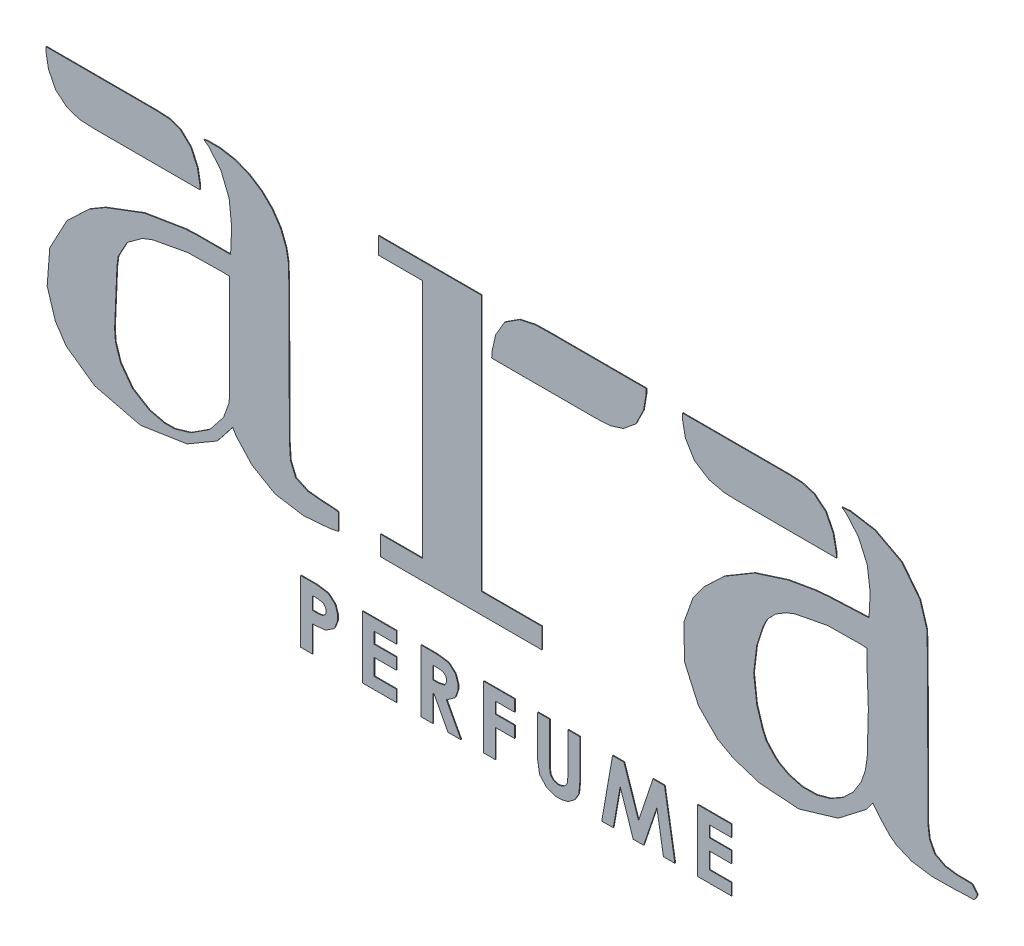
SolidWorks part; units mm, degrees
ref_plane "Front Plane" through (0, 0, 0) normal (0, 0, 1) x (1, 0, 0)
ref_plane "Top Plane" through (0, 0, 0) normal (0, 1, 0) x (1, 0, 0)
ref_plane "Right Plane" through (0, 0, 0) normal (1, 0, 0) x (0, 0, -1)
sketch "Model" plane through (0, 0, 0) normal (0, 0, 1) x (1, 0, 0)
  line L0 (1544.5765, 1861.6625) -> (1535.651, 1862.3255)
  line L1 (1535.651, 1862.3255) -> (1490.4999, 1861.7616)
  line L2 (1490.4999, 1861.7616) -> (1445.6232, 1853.1586)
  line L3 (1445.6232, 1853.1586) -> (1436.8704, 1849.7626)
  line L4 (1436.8704, 1849.7626) -> (1433.8681, 1848.6425)
  line L5 (1433.8681, 1848.6425) -> (1418.9837, 1839.6458)
  line L6 (1418.9837, 1839.6458) -> (1407.3708, 1827.4614)
  line L7 (1407.3708, 1827.4614) -> (1406.0373, 1824.736)
  line L8 (1406.0373, 1824.736) -> (1401.9784, 1816.4378)
  line L9 (1401.9784, 1816.4378) -> (1393.2941, 1789.7983)
  line L10 (1393.2941, 1789.7983) -> (1389.0295, 1754.5583)
  line L11 (1389.0295, 1754.5583) -> (1393.1875, 1719.1634)
  line L12 (1393.1875, 1719.1634) -> (1401.6634, 1692.3182)
  line L13 (1401.6634, 1692.3182) -> (1405.6512, 1683.8854)
  line L14 (1405.6512, 1683.8854) -> (1406.3497, 1682.3436)
  line L15 (1406.3497, 1682.3436) -> (1418.43, 1669.0823)
  line L16 (1418.43, 1669.0823) -> (1419.7914, 1667.9621)
  line L17 (1419.7914, 1667.9621) -> (1423.6802, 1664.7719)
  line L18 (1423.6802, 1664.7719) -> (1437.2539, 1657.4262)
  line L19 (1437.2539, 1657.4262) -> (1456.1972, 1652.4173)
  line L20 (1456.1972, 1652.4173) -> (1475.5876, 1652.6942)
  line L21 (1475.5876, 1652.6942) -> (1494.3531, 1657.8809)
  line L22 (1494.3531, 1657.8809) -> (1511.5032, 1667.6395)
  line L23 (1511.5032, 1667.6395) -> (1526.0625, 1681.6451)
  line L24 (1526.0625, 1681.6451) -> (1536.9413, 1699.5318)
  line L25 (1536.9413, 1699.5318) -> (1542.3718, 1715.4906)
  line L26 (1542.3718, 1715.4906) -> (1543.2126, 1720.9541)
  line L27 (1543.2126, 1720.9541) -> (1544.9601, 1732.3613)
  line L28 (1544.9601, 1732.3613) -> (1546.5019, 1790.4993)
  line L29 (1546.5019, 1790.4993) -> (1544.5765, 1843.8774)
  line L30 (1544.5765, 1843.8774) -> (1544.5765, 1861.6625)
  line L31 (1552.4175, 1681.7899) -> (1543.3116, 1669.3617)
  line L32 (1543.3116, 1669.3617) -> (1505.1938, 1639.9256)
  line L33 (1505.1938, 1639.9256) -> (1451.0817, 1623.822)
  line L34 (1451.0817, 1623.822) -> (1397.0406, 1627.6041)
  line L35 (1397.0406, 1627.6041) -> (1360.8837, 1639.3236)
  line L36 (1360.8837, 1639.3236) -> (1350.0329, 1645.3104)
  line L37 (1350.0329, 1645.3104) -> (1339.5681, 1651.0889)
  line L38 (1339.5681, 1651.0889) -> (1313.3121, 1677.5506)
  line L39 (1313.3121, 1677.5506) -> (1293.9217, 1720.4995)
  line L40 (1293.9217, 1720.4995) -> (1293.2943, 1767.5758)
  line L41 (1293.2943, 1767.5758) -> (1305.8572, 1802.6482)
  line L42 (1305.8572, 1802.6482) -> (1312.9006, 1812.2367)
  line L43 (1312.9006, 1812.2367) -> (1320.3834, 1822.5313)
  line L44 (1320.3834, 1822.5313) -> (1348.4911, 1849.3054)
  line L45 (1348.4911, 1849.3054) -> (1390.1141, 1873.9841)
  line L46 (1390.1141, 1873.9841) -> (1436.4589, 1888.8227)
  line L47 (1436.4589, 1888.8227) -> (1473.8045, 1895.2286)
  line L48 (1473.8045, 1895.2286) -> (1486.3318, 1896.3488)
  line L49 (1486.3318, 1896.3488) -> (1491.3051, 1896.806)
  line L50 (1491.3051, 1896.806) -> (1541.9502, 1899.1097)
  line L51 (1541.9502, 1899.1097) -> (1547.1292, 1899.3612)
  line L52 (1547.1292, 1899.3612) -> (1548.0081, 1907.2987)
  line L53 (1548.0081, 1907.2987) -> (1548.8768, 1931.3144)
  line L54 (1548.8768, 1931.3144) -> (1545.0337, 1961.1696)
  line L55 (1545.0337, 1961.1696) -> (1532.9535, 1988.3653)
  line L56 (1532.9535, 1988.3653) -> (1516.573, 2007.4433)
  line L57 (1516.573, 2007.4433) -> (1510.0605, 2012.3785)
  line L58 (1510.0605, 2012.3785) -> (1521.2974, 2013.1862)
  line L59 (1521.2974, 2013.1862) -> (1555.6332, 2007.55)
  line L60 (1555.6332, 2007.55) -> (1592.4606, 1987.8802)
  line L61 (1592.4606, 1987.8802) -> (1617.345, 1955.9905)
  line L62 (1617.345, 1955.9905) -> (1626.87, 1924.906)
  line L63 (1626.87, 1924.906) -> (1627.1469, 1914.4767)
  line L64 (1627.1469, 1914.4767) -> (1627.6041, 1896.5901)
  line L65 (1627.6041, 1896.5901) -> (1628.3737, 1717.487)
  line L66 (1628.3737, 1717.487) -> (1628.4016, 1699.5673)
  line L67 (1628.4016, 1699.5673) -> (1628.4016, 1694.0733)
  line L68 (1628.4016, 1694.0733) -> (1630.5073, 1677.5506)
  line L69 (1630.5073, 1677.5506) -> (1637.7209, 1663.5095)
  line L70 (1637.7209, 1663.5095) -> (1651.4394, 1656.0546)
  line L71 (1651.4394, 1656.0546) -> (1667.7488, 1653.7864)
  line L72 (1667.7488, 1653.7864) -> (1673.2047, 1653.7153)
  line L73 (1673.2047, 1653.7153) -> (1674.5026, 1653.7153)
  line L74 (1674.5026, 1653.7153) -> (1687.5227, 1653.4994)
  line L75 (1687.5227, 1653.4994) -> (1688.7165, 1653.1158)
  line L76 (1688.7165, 1653.1158) -> (1689.4861, 1652.872)
  line L77 (1689.4861, 1652.872) -> (1695.8208, 1645.2393)
  line L78 (1695.8208, 1645.2393) -> (1695.991, 1644.3706)
  line L79 (1695.991, 1644.3706) -> (1696.0977, 1643.7686)
  line L80 (1696.0977, 1643.7686) -> (1694.2791, 1639.2525)
  line L81 (1694.2791, 1639.2525) -> (1691.2692, 1636.0013)
  line L82 (1691.2692, 1636.0013) -> (1690.812, 1636.0013)
  line L83 (1690.812, 1636.0013) -> (1683.6441, 1636.108)
  line L84 (1683.6441, 1636.108) -> (1662.1125, 1635.2291)
  line L85 (1662.1125, 1635.2291) -> (1633.4816, 1634.9523)
  line L86 (1633.4816, 1634.9523) -> (1605.6229, 1639.2525)
  line L87 (1605.6229, 1639.2525) -> (1585.0413, 1647.9723)
  line L88 (1585.0413, 1647.9723) -> (1579.2272, 1652.2446)
  line L89 (1579.2272, 1652.2446) -> (1576.672, 1654.1369)
  line L90 (1576.672, 1654.1369) -> (1565.5442, 1665.8565)
  line L91 (1565.5442, 1665.8565) -> (1554.7645, 1679.1635)
  line L92 (1554.7645, 1679.1635) -> (1552.4175, 1681.7899)
  line L93 (669.2773, 1866.3488) -> (659.6151, 1866.806)
  line L94 (659.6151, 1866.806) -> (611.4542, 1865.9653)
  line L95 (611.4542, 1865.9653) -> (563.9206, 1857.1464)
  line L96 (563.9206, 1857.1464) -> (554.6446, 1853.6082)
  line L97 (554.6446, 1853.6082) -> (549.463, 1851.6549)
  line L98 (549.463, 1851.6549) -> (528.3581, 1836.1787)
  line L99 (528.3581, 1836.1787) -> (516.1763, 1813.7073)
  line L100 (516.1763, 1813.7073) -> (515.5133, 1808.2489)
  line L101 (515.5133, 1808.2489) -> (514.5329, 1800.7584)
  line L102 (514.5329, 1800.7584) -> (511.3122, 1724.8708)
  line L103 (511.3122, 1724.8708) -> (511.9065, 1717.3448)
  line L104 (511.9065, 1717.3448) -> (512.4323, 1710.0677)
  line L105 (512.4323, 1710.0677) -> (519.4681, 1688.5361)
  line L106 (519.4681, 1688.5361) -> (535.9883, 1666.2781)
  line L107 (535.9883, 1666.2781) -> (559.1581, 1652.0312)
  line L108 (559.1581, 1652.0312) -> (579.9506, 1647.1646)
  line L109 (579.9506, 1647.1646) -> (586.8467, 1647.2357)
  line L110 (586.8467, 1647.2357) -> (594.1619, 1647.3449)
  line L111 (594.1619, 1647.3449) -> (616.1075, 1653.8499)
  line L112 (616.1075, 1653.8499) -> (642.1145, 1670.7231)
  line L113 (642.1145, 1670.7231) -> (661.0147, 1694.7718)
  line L114 (661.0147, 1694.7718) -> (668.6118, 1715.7395)
  line L115 (668.6118, 1715.7395) -> (668.8912, 1722.8109)
  line L116 (668.8912, 1722.8109) -> (669.2773, 1734.5304)
  line L117 (669.2773, 1734.5304) -> (669.2773, 1833.4101)
  line L118 (669.2773, 1833.4101) -> (669.2773, 1866.3488)
  line L119 (670.5016, 1893.0239) -> (671.1315, 1901.5634)
  line L120 (671.1315, 1901.5634) -> (671.9367, 1927.2555)
  line L121 (671.9367, 1927.2555) -> (668.6474, 1958.7591)
  line L122 (668.6474, 1958.7591) -> (657.0955, 1987.0395)
  line L123 (657.0955, 1987.0395) -> (640.5042, 2006.5365)
  line L124 (640.5042, 2006.5365) -> (633.8189, 2011.4387)
  line L125 (633.8189, 2011.4387) -> (639.1402, 2012.2083)
  line L126 (639.1402, 2012.2083) -> (655.5562, 2012.2363)
  line L127 (655.5562, 2012.2363) -> (676.4528, 2008.599)
  line L128 (676.4528, 2008.599) -> (695.8432, 2000.9739)
  line L129 (695.8432, 2000.9739) -> (713.1329, 1989.8081)
  line L130 (713.1329, 1989.8081) -> (727.8014, 1975.5968)
  line L131 (727.8014, 1975.5968) -> (739.2111, 1958.7235)
  line L132 (739.2111, 1958.7235) -> (746.8057, 1939.6837)
  line L133 (746.8057, 1939.6837) -> (749.7826, 1924.1364)
  line L134 (749.7826, 1924.1364) -> (749.9553, 1918.9217)
  line L135 (749.9553, 1918.9217) -> (750.5167, 1902.3355)
  line L136 (750.5167, 1902.3355) -> (751.2863, 1736.1789)
  line L137 (751.2863, 1736.1789) -> (751.3574, 1719.5495)
  line L138 (751.3574, 1719.5495) -> (751.3574, 1711.9956)
  line L139 (751.3574, 1711.9956) -> (752.8966, 1689.2092)
  line L140 (752.8966, 1689.2092) -> (760.001, 1672.1912)
  line L141 (760.001, 1672.1912) -> (776.5237, 1664.495)
  line L142 (776.5237, 1664.495) -> (798.8529, 1662.2903)
  line L143 (798.8529, 1662.2903) -> (806.3459, 1662.0388)
  line L144 (806.3459, 1662.0388) -> (807.2907, 1662.0388)
  line L145 (807.2907, 1662.0388) -> (817.4761, 1661.0279)
  line L146 (817.4761, 1661.0279) -> (818.7004, 1660.8831)
  line L147 (818.7004, 1660.8831) -> (818.7004, 1655.1478)
  line L148 (818.7004, 1655.1478) -> (818.7004, 1642.2014)
  line L149 (818.7004, 1642.2014) -> (818.7004, 1637.8555)
  line L150 (818.7004, 1637.8555) -> (806.9758, 1635.4095)
  line L151 (806.9758, 1635.4095) -> (770.8875, 1632.5063)
  line L152 (770.8875, 1632.5063) -> (731.7562, 1638.841)
  line L153 (731.7562, 1638.841) -> (699.7649, 1657.4973)
  line L154 (699.7649, 1657.4973) -> (678.8328, 1680.4183)
  line L155 (678.8328, 1680.4183) -> (673.4073, 1689.0289)
  line L156 (673.4073, 1689.0289) -> (672.3583, 1687.703)
  line L157 (672.3583, 1687.703) -> (662.3456, 1674.8531)
  line L158 (662.3456, 1674.8531) -> (661.3652, 1673.5908)
  line L159 (661.3652, 1673.5908) -> (652.0891, 1662.0033)
  line L160 (652.0891, 1662.0033) -> (610.7532, 1637.8911)
  line L161 (610.7532, 1637.8911) -> (546.768, 1628.0892)
  line L162 (546.768, 1628.0892) -> (483.8344, 1643.5984)
  line L163 (483.8344, 1643.5984) -> (444.7362, 1671.3225)
  line L164 (444.7362, 1671.3225) -> (436.5117, 1683.705)
  line L165 (436.5117, 1683.705) -> (429.8264, 1693.7253)
  line L166 (429.8264, 1693.7253) -> (418.6961, 1729.6282)
  line L167 (418.6961, 1729.6282) -> (422.2674, 1776.9942)
  line L168 (422.2674, 1776.9942) -> (445.8564, 1820.992)
  line L169 (445.8564, 1820.992) -> (476.311, 1849.8617)
  line L170 (476.311, 1849.8617) -> (488.0712, 1856.7984)
  line L171 (488.0712, 1856.7984) -> (498.2566, 1862.8182)
  line L172 (498.2566, 1862.8182) -> (552.0538, 1883.1154)
  line L173 (552.0538, 1883.1154) -> (608.8278, 1892.3889)
  line L174 (608.8278, 1892.3889) -> (620.5525, 1892.8817)
  line L175 (620.5525, 1892.8817) -> (624.5784, 1893.062)
  line L176 (624.5784, 1893.062) -> (659.0208, 1893.0239)
  line L177 (659.0208, 1893.0239) -> (670.5016, 1893.0239)
  line L178 (933.9936, 1993.7959) -> (918.9136, 1993.7959)
  line L179 (918.9136, 1993.7959) -> (884.9944, 1993.7959)
  line L180 (884.9944, 1993.7959) -> (873.7244, 1993.7959)
  line L181 (873.7244, 1993.7959) -> (873.7244, 1999.6023)
  line L182 (873.7244, 1999.6023) -> (873.7244, 2012.6223)
  line L183 (873.7244, 2012.6223) -> (873.7244, 2016.9302)
  line L184 (873.7244, 2016.9302) -> (909.0406, 2016.9302)
  line L185 (909.0406, 2016.9302) -> (988.4918, 2016.9302)
  line L186 (988.4918, 2016.9302) -> (1014.9891, 2016.9302)
  line L187 (1014.9891, 2016.9302) -> (1014.9891, 1928.8658)
  line L188 (1014.9891, 1928.8658) -> (1014.9891, 1730.6519)
  line L189 (1014.9891, 1730.6519) -> (1014.9891, 1664.5661)
  line L190 (1014.9891, 1664.5661) -> (1035.7866, 1664.5661)
  line L191 (1035.7866, 1664.5661) -> (1082.5785, 1664.5661)
  line L192 (1082.5785, 1664.5661) -> (1098.1969, 1664.5661)
  line L193 (1098.1969, 1664.5661) -> (1098.1969, 1657.5583)
  line L194 (1098.1969, 1657.5583) -> (1098.1969, 1641.8154)
  line L195 (1098.1969, 1641.8154) -> (1098.1969, 1636.5652)
  line L196 (1098.1969, 1636.5652) -> (1042.7487, 1636.5652)
  line L197 (1042.7487, 1636.5652) -> (917.9992, 1636.5652)
  line L198 (917.9992, 1636.5652) -> (876.4194, 1636.5652)
  line L199 (876.4194, 1636.5652) -> (876.4194, 1643.286)
  line L200 (876.4194, 1643.286) -> (876.4194, 1658.4016)
  line L201 (876.4194, 1658.4016) -> (876.4194, 1663.4104)
  line L202 (876.4194, 1663.4104) -> (890.8059, 1663.4104)
  line L203 (890.8059, 1663.4104) -> (923.1782, 1663.4104)
  line L204 (923.1782, 1663.4104) -> (933.9936, 1663.4104)
  line L205 (933.9936, 1663.4104) -> (933.9936, 1746.0087)
  line L206 (933.9936, 1746.0087) -> (933.9936, 1931.8783)
  line L207 (933.9936, 1931.8783) -> (933.9936, 1993.7959)
  line L208 (1029.2004, 1949.163) -> (1029.5865, 1956.7982)
  line L209 (1029.5865, 1956.7982) -> (1034.5598, 1979.4398)
  line L210 (1034.5598, 1979.4398) -> (1047.1937, 2001.0095)
  line L211 (1047.1937, 2001.0095) -> (1067.4274, 2014.0295)
  line L212 (1067.4274, 2014.0295) -> (1088.5653, 2018.6777)
  line L213 (1088.5653, 2018.6777) -> (1095.6341, 2018.8225)
  line L214 (1095.6341, 2018.8225) -> (1107.7499, 2019.0993)
  line L215 (1107.7499, 2019.0993) -> (1207.8919, 2019.0282)
  line L216 (1207.8919, 2019.0282) -> (1241.2777, 2019.0282)
  line L217 (1241.2777, 2019.0282) -> (1241.2777, 2012.1372)
  line L218 (1241.2777, 2012.1372) -> (1237.7496, 1991.3752)
  line L219 (1237.7496, 1991.3752) -> (1227.2112, 1969.9605)
  line L220 (1227.2112, 1969.9605) -> (1209.8807, 1955.7848)
  line L221 (1209.8807, 1955.7848) -> (1192.0322, 1950.1841)
  line L222 (1192.0322, 1950.1841) -> (1186.0098, 1949.8615)
  line L223 (1186.0098, 1949.8615) -> (1173.0634, 1949.1985)
  line L224 (1173.0634, 1949.1985) -> (1065.149, 1949.163)
  line L225 (1065.149, 1949.163) -> (1029.2004, 1949.163)
  line L226 (1291.1252, 2014.8245) -> (1330.8228, 2014.8245)
  line L227 (1330.8228, 2014.8245) -> (1436.8704, 2014.8245)
  line L228 (1436.8704, 2014.8245) -> (1449.9971, 2014.1997)
  line L229 (1449.9971, 2014.1997) -> (1455.5343, 2013.9558)
  line L230 (1455.5343, 2013.9558) -> (1472.0138, 2008.947)
  line L231 (1472.0138, 2008.947) -> (1488.0158, 1995.8558)
  line L232 (1488.0158, 1995.8558) -> (1498.1961, 1975.4164)
  line L233 (1498.1961, 1975.4164) -> (1502.3262, 1954.977)
  line L234 (1502.3262, 1954.977) -> (1502.7123, 1948.0784)
  line L235 (1502.7123, 1948.0784) -> (1488.7524, 1948.0784)
  line L236 (1488.7524, 1948.0784) -> (1451.5033, 1948.0784)
  line L237 (1451.5033, 1948.0784) -> (1446.8881, 1948.0784)
  line L238 (1446.8881, 1948.0784) -> (1439.2173, 1948.114)
  line L239 (1439.2173, 1948.114) -> (1362.7405, 1948.3654)
  line L240 (1362.7405, 1948.3654) -> (1355.1052, 1948.6778)
  line L241 (1355.1052, 1948.6778) -> (1348.1075, 1948.9572)
  line L242 (1348.1075, 1948.9572) -> (1327.3532, 1953.9306)
  line L243 (1327.3532, 1953.9306) -> (1307.3278, 1966.9125)
  line L244 (1307.3278, 1966.9125) -> (1295.1866, 1987.3163)
  line L245 (1295.1866, 1987.3163) -> (1291.0896, 2007.9716)
  line L246 (1291.0896, 2007.9716) -> (1291.1252, 2014.8245)
  line L247 (417.0858, 2013.4986) -> (458.3887, 2013.4986)
  line L248 (458.3887, 2013.4986) -> (568.5409, 2013.392)
  line L249 (568.5409, 2013.392) -> (582.2975, 2012.6223)
  line L250 (582.2975, 2012.6223) -> (587.1616, 2012.3785)
  line L251 (587.1616, 2012.3785) -> (601.6523, 2006.9861)
  line L252 (601.6523, 2006.9861) -> (616.0033, 1993.4098)
  line L253 (616.0033, 1993.4098) -> (625.0686, 1973.5267)
  line L254 (625.0686, 1973.5267) -> (628.3579, 1955.1117)
  line L255 (628.3579, 1955.1117) -> (628.4976, 1948.9572)
  line L256 (628.4976, 1948.9572) -> (588.5967, 1948.9572)
  line L257 (588.5967, 1948.9572) -> (482.1555, 1949.0284)
  line L258 (482.1555, 1949.0284) -> (468.9246, 1949.7624)
  line L259 (468.9246, 1949.7624) -> (463.2528, 1950.0774)
  line L260 (463.2528, 1950.0774) -> (446.5218, 1955.3987)
  line L261 (446.5218, 1955.3987) -> (430.3878, 1968.66)
  line L262 (430.3878, 1968.66) -> (420.5503, 1988.4009)
  line L263 (420.5503, 1988.4009) -> (417.1569, 2007.235)
  line L264 (417.1569, 2007.235) -> (417.0858, 2013.4986)
  line L265 (342.1812, 2090.5775) -> (1770.9363, 2090.5775)
  line L266 (1770.9363, 2090.5775) -> (1770.9363, 1410.9751)
  line L267 (1770.9363, 1410.9751) -> (342.1812, 1410.9751)
  line L268 (342.1812, 1410.9751) -> (342.1812, 2090.5775)
  line L269 (351.9119, 1511.8512) -> (701.7233, 1511.8512)
  line L270 (766.8971, 1474.0484) -> (783.0693, 1474.0484)
  line L271 (783.0693, 1474.0484) -> (783.0693, 1510.1672)
  line L272 (783.0693, 1510.1672) -> (787.3746, 1510.1672)
  line L273 (787.3746, 1510.1672) -> (799.4853, 1511.3229)
  line L274 (799.4853, 1511.3229) -> (800.2905, 1511.5032)
  line L275 (800.2905, 1511.5032) -> (801.6189, 1511.8867)
  line L276 (801.6189, 1511.8867) -> (812.226, 1518.8133)
  line L277 (812.226, 1518.8133) -> (813.0311, 1519.7912)
  line L278 (813.0311, 1519.7912) -> (813.8008, 1520.8123)
  line L279 (813.8008, 1520.8123) -> (817.6844, 1531.206)
  line L280 (817.6844, 1531.206) -> (817.6844, 1534.6756)
  line L281 (817.6844, 1534.6756) -> (817.6844, 1538.1326)
  line L282 (817.6844, 1538.1326) -> (814.7101, 1547.5509)
  line L283 (814.7101, 1547.5509) -> (814.1157, 1548.4653)
  line L284 (814.1157, 1548.4653) -> (813.5214, 1549.4406)
  line L285 (813.5214, 1549.4406) -> (805.3654, 1556.4028)
  line L286 (805.3654, 1556.4028) -> (804.3494, 1556.7889)
  line L287 (804.3494, 1556.7889) -> (803.3004, 1557.2461)
  line L288 (803.3004, 1557.2461) -> (788.9138, 1559.4152)
  line L289 (788.9138, 1559.4152) -> (784.1183, 1559.4152)
  line L290 (784.1183, 1559.4152) -> (766.8971, 1559.4152)
  line L291 (766.8971, 1559.4152) -> (766.8971, 1474.0484)
  line L292 (783.0693, 1543.5986) -> (787.6896, 1543.5986)
  line L293 (787.6896, 1543.5986) -> (790.2778, 1543.5986)
  line L294 (790.2778, 1543.5986) -> (797.6641, 1542.1915)
  line L295 (797.6641, 1542.1915) -> (798.1544, 1541.9146)
  line L296 (798.1544, 1541.9146) -> (798.7843, 1541.5285)
  line L297 (798.7843, 1541.5285) -> (801.9694, 1536.385)
  line L298 (801.9694, 1536.385) -> (801.9694, 1534.6756)
  line L299 (801.9694, 1534.6756) -> (801.9694, 1533.4818)
  line L300 (801.9694, 1533.4818) -> (800.7452, 1530.1595)
  line L301 (800.7452, 1530.1595) -> (800.5343, 1529.809)
  line L302 (800.5343, 1529.809) -> (800.3235, 1529.4585)
  line L303 (800.3235, 1529.4585) -> (797.245, 1527.0048)
  line L304 (797.245, 1527.0048) -> (796.859, 1526.8346)
  line L305 (796.859, 1526.8346) -> (796.4399, 1526.6899)
  line L306 (796.4399, 1526.6899) -> (790.3134, 1526.0269)
  line L307 (790.3134, 1526.0269) -> (788.2839, 1526.0269)
  line L308 (788.2839, 1526.0269) -> (783.0693, 1526.0269)
  line L309 (783.0693, 1526.0269) -> (783.0693, 1543.5986)
  line L310 (851.568, 1474.0484) -> (898.2227, 1474.0484)
  line L311 (898.2227, 1474.0484) -> (898.2227, 1489.9335)
  line L312 (898.2227, 1489.9335) -> (867.7732, 1489.9335)
  line L313 (867.7732, 1489.9335) -> (867.7732, 1512.443)
  line L314 (867.7732, 1512.443) -> (898.2227, 1512.443)
  line L315 (898.2227, 1512.443) -> (898.2227, 1528.125)
  line L316 (898.2227, 1528.125) -> (867.7732, 1528.125)
  line L317 (867.7732, 1528.125) -> (867.7732, 1543.5275)
  line L318 (867.7732, 1543.5275) -> (898.2227, 1543.5275)
  line L319 (898.2227, 1543.5275) -> (898.2227, 1559.4152)
  line L320 (898.2227, 1559.4152) -> (851.568, 1559.4152)
  line L321 (851.568, 1559.4152) -> (851.568, 1474.0484)
  line L322 (932.246, 1474.0484) -> (948.4208, 1474.0484)
  line L323 (948.4208, 1474.0484) -> (948.4208, 1510.1672)
  line L324 (948.4208, 1510.1672) -> (950.0616, 1510.1672)
  line L325 (950.0616, 1510.1672) -> (969.2107, 1474.0484)
  line L326 (969.2107, 1474.0484) -> (987.0592, 1474.0484)
  line L327 (987.0592, 1474.0484) -> (966.8256, 1511.9502)
  line L328 (966.8256, 1511.9502) -> (968.1972, 1512.443)
  line L329 (968.1972, 1512.443) -> (978.314, 1519.5855)
  line L330 (978.314, 1519.5855) -> (978.977, 1520.5253)
  line L331 (978.977, 1520.5253) -> (979.6399, 1521.4752)
  line L332 (979.6399, 1521.4752) -> (983.0359, 1531.3762)
  line L333 (983.0359, 1531.3762) -> (983.0359, 1534.6756)
  line L334 (983.0359, 1534.6756) -> (983.0359, 1538.1326)
  line L335 (983.0359, 1538.1326) -> (979.9523, 1547.4798)
  line L336 (979.9523, 1547.4798) -> (979.3249, 1548.4653)
  line L337 (979.3249, 1548.4653) -> (978.7357, 1549.4762)
  line L338 (978.7357, 1549.4762) -> (970.7143, 1556.5476)
  line L339 (970.7143, 1556.5476) -> (969.7034, 1556.9692)
  line L340 (969.7034, 1556.9692) -> (968.6798, 1557.3883)
  line L341 (968.6798, 1557.3883) -> (954.2628, 1559.4152)
  line L342 (954.2628, 1559.4152) -> (949.4698, 1559.4152)
  line L343 (949.4698, 1559.4152) -> (932.246, 1559.4152)
  line L344 (932.246, 1559.4152) -> (932.246, 1474.0484)
  line L345 (948.4208, 1543.5986) -> (952.9369, 1543.5986)
  line L346 (952.9369, 1543.5986) -> (955.1772, 1543.5986)
  line L347 (955.1772, 1543.5986) -> (961.5475, 1542.829)
  line L348 (961.5475, 1542.829) -> (961.9615, 1542.6487)
  line L349 (961.9615, 1542.6487) -> (962.345, 1542.5141)
  line L350 (962.345, 1542.5141) -> (965.6064, 1540.0604)
  line L351 (965.6064, 1540.0604) -> (965.8858, 1539.6743)
  line L352 (965.8858, 1539.6743) -> (966.0915, 1539.3619)
  line L353 (966.0915, 1539.3619) -> (967.3184, 1535.9659)
  line L354 (967.3184, 1535.9659) -> (967.3184, 1534.8077)
  line L355 (967.3184, 1534.8077) -> (967.3184, 1533.1338)
  line L356 (967.3184, 1533.1338) -> (964.8368, 1528.4018)
  line L357 (964.8368, 1528.4018) -> (964.344, 1528.0157)
  line L358 (964.344, 1528.0157) -> (963.8513, 1527.7033)
  line L359 (963.8513, 1527.7033) -> (956.0814, 1526.0269)
  line L360 (956.0814, 1526.0269) -> (953.5287, 1526.0269)
  line L361 (953.5287, 1526.0269) -> (948.4208, 1526.0269)
  line L362 (948.4208, 1526.0269) -> (948.4208, 1543.5986)
  line L363 (1018.2504, 1474.0484) -> (1034.415, 1474.0484)
  line L364 (1034.415, 1474.0484) -> (1034.415, 1512.443)
  line L365 (1034.415, 1512.443) -> (1060.5973, 1512.443)
  line L366 (1060.5973, 1512.443) -> (1060.5973, 1528.125)
  line L367 (1060.5973, 1528.125) -> (1034.415, 1528.125)
  line L368 (1034.415, 1528.125) -> (1034.415, 1543.6977)
  line L369 (1034.415, 1543.6977) -> (1060.5973, 1543.6977)
  line L370 (1060.5973, 1543.6977) -> (1060.5973, 1559.4152)
  line L371 (1060.5973, 1559.4152) -> (1018.2504, 1559.4152)
  line L372 (1018.2504, 1559.4152) -> (1018.2504, 1474.0484)
  line L373 (1092.3448, 1508.5263) -> (1092.3448, 1503.1339)
  line L374 (1092.3448, 1503.1339) -> (1094.801, 1487.9447)
  line L375 (1094.801, 1487.9447) -> (1095.3191, 1486.8601)
  line L376 (1095.3191, 1486.8601) -> (1095.7763, 1485.8035)
  line L377 (1095.7763, 1485.8035) -> (1104.0034, 1476.8779)
  line L378 (1104.0034, 1476.8779) -> (1105.1946, 1476.1439)
  line L379 (1105.1946, 1476.1439) -> (1106.3148, 1475.4454)
  line L380 (1106.3148, 1475.4454) -> (1117.5162, 1471.9148)
  line L381 (1117.5162, 1471.9148) -> (1121.2601, 1471.9148)
  line L382 (1121.2601, 1471.9148) -> (1124.3716, 1471.9148)
  line L383 (1124.3716, 1471.9148) -> (1132.8476, 1473.769)
  line L384 (1132.8476, 1473.769) -> (1133.7519, 1474.155)
  line L385 (1133.7519, 1474.155) -> (1134.6307, 1474.5411)
  line L386 (1134.6307, 1474.5411) -> (1142.4361, 1480.2383)
  line L387 (1142.4361, 1480.2383) -> (1143.1346, 1481.0105)
  line L388 (1143.1346, 1481.0105) -> (1143.7976, 1481.8157)
  line L389 (1143.7976, 1481.8157) -> (1148.4915, 1489.8726)
  line L390 (1148.4915, 1489.8726) -> (1148.7353, 1490.6701)
  line L391 (1148.7353, 1490.6701) -> (1148.9487, 1491.5109)
  line L392 (1148.9487, 1491.5109) -> (1150.1679, 1504.2896)
  line L393 (1150.1679, 1504.2896) -> (1150.1679, 1508.5263)
  line L394 (1150.1679, 1508.5263) -> (1150.1679, 1559.4152)
  line L395 (1150.1679, 1559.4152) -> (1133.8585, 1559.4152)
  line L396 (1133.8585, 1559.4152) -> (1133.8585, 1506.2886)
  line L397 (1133.8585, 1506.2886) -> (1133.8585, 1503.3752)
  line L398 (1133.8585, 1503.3752) -> (1132.8832, 1495.1481)
  line L399 (1132.8832, 1495.1481) -> (1132.6673, 1494.63)
  line L400 (1132.6673, 1494.63) -> (1132.4615, 1494.1372)
  line L401 (1132.4615, 1494.1372) -> (1128.8878, 1489.9335)
  line L402 (1128.8878, 1489.9335) -> (1128.4026, 1489.5855)
  line L403 (1128.4026, 1489.5855) -> (1127.8387, 1489.2706)
  line L404 (1127.8387, 1489.2706) -> (1122.6952, 1487.5967)
  line L405 (1122.6952, 1487.5967) -> (1121.0112, 1487.5967)
  line L406 (1121.0112, 1487.5967) -> (1119.2637, 1487.5967)
  line L407 (1119.2637, 1487.5967) -> (1114.4682, 1489.1004)
  line L408 (1114.4682, 1489.1004) -> (1114.011, 1489.3798)
  line L409 (1114.011, 1489.3798) -> (1113.5284, 1489.6922)
  line L410 (1113.5284, 1489.6922) -> (1110.168, 1493.6165)
  line L411 (1110.168, 1493.6165) -> (1109.9521, 1494.1017)
  line L412 (1109.9521, 1494.1017) -> (1109.7463, 1494.5944)
  line L413 (1109.7463, 1494.5944) -> (1108.6617, 1501.8334)
  line L414 (1108.6617, 1501.8334) -> (1108.6617, 1504.2185)
  line L415 (1108.6617, 1504.2185) -> (1108.6617, 1559.4152)
  line L416 (1108.6617, 1559.4152) -> (1092.3448, 1559.4152)
  line L417 (1092.3448, 1559.4152) -> (1092.3448, 1508.5263)
  line L418 (1180.3736, 1474.0484) -> (1196.1978, 1474.0484)
  line L419 (1196.1978, 1474.0484) -> (1205.6161, 1527.9192)
  line L420 (1205.6161, 1527.9192) -> (1223.5739, 1474.0484)
  line L421 (1223.5739, 1474.0484) -> (1237.8563, 1474.0484)
  line L422 (1237.8563, 1474.0484) -> (1256.0554, 1527.9192)
  line L423 (1256.0554, 1527.9192) -> (1265.0876, 1474.0484)
  line L424 (1265.0876, 1474.0484) -> (1280.8052, 1474.0484)
  line L425 (1280.8052, 1474.0484) -> (1266.5202, 1559.4152)
  line L426 (1266.5202, 1559.4152) -> (1250.696, 1559.4152)
  line L427 (1250.696, 1559.4152) -> (1230.8129, 1499.8446)
  line L428 (1230.8129, 1499.8446) -> (1210.8307, 1559.4152)
  line L429 (1210.8307, 1559.4152) -> (1195.1487, 1559.4152)
  line L430 (1195.1487, 1559.4152) -> (1180.3736, 1474.0484)
  line L431 (1311.9506, 1474.0484) -> (1358.5723, 1474.0484)
  line L432 (1358.5723, 1474.0484) -> (1358.5723, 1489.9335)
  line L433 (1358.5723, 1489.9335) -> (1328.1254, 1489.9335)
  line L434 (1328.1254, 1489.9335) -> (1328.1254, 1512.443)
  line L435 (1328.1254, 1512.443) -> (1358.5723, 1512.443)
  line L436 (1358.5723, 1512.443) -> (1358.5723, 1528.125)
  line L437 (1358.5723, 1528.125) -> (1328.1254, 1528.125)
  line L438 (1328.1254, 1528.125) -> (1328.1254, 1543.5275)
  line L439 (1328.1254, 1543.5275) -> (1358.5723, 1543.5275)
  line L440 (1358.5723, 1543.5275) -> (1358.5723, 1559.4152)
  line L441 (1358.5723, 1559.4152) -> (1311.9506, 1559.4152)
  line L442 (1311.9506, 1559.4152) -> (1311.9506, 1474.0484)
  line L443 (1416.4666, 1511.8512) -> (1766.2779, 1511.8512)
  line L444 (0, 7.2105) -> (0, 22.5414)
  line L445 (0, 22.5414) -> (24.1165, 22.5414)
  line L446 (24.1165, 22.5414) -> (27.3718, 22.5414)
  line L447 (27.3718, 22.5414) -> (36.5072, 25.9367)
  line L448 (36.5072, 25.9367) -> (37.1373, 26.6017)
  line L449 (37.1373, 26.6017) -> (37.7325, 27.3017)
  line L450 (37.7325, 27.3017) -> (40.7426, 38.8523)
  line L451 (40.7426, 38.8523) -> (40.7426, 42.6677)
  line L452 (40.7426, 42.6677) -> (40.7426, 287.8938)
  line L453 (40.7426, 287.8938) -> (40.7426, 291.1831)
  line L454 (40.7426, 291.1831) -> (37.3824, 300.5277)
  line L455 (37.3824, 300.5277) -> (36.7172, 301.0535)
  line L456 (36.7172, 301.0535) -> (36.0523, 301.6148)
  line L457 (36.0523, 301.6148) -> (24.0815, 304.2387)
  line L458 (24.0815, 304.2387) -> (20.1262, 304.2387)
  line L459 (20.1262, 304.2387) -> (0.9451, 304.2387)
  line L460 (0.9451, 304.2387) -> (0.9451, 318.6252)
  line L461 (0.9451, 318.6252) -> (127.0579, 318.6252)
  line L462 (127.0579, 318.6252) -> (258.2469, 139.239)
  line L463 (258.2469, 139.239) -> (258.2469, 281.0688)
  line L464 (258.2469, 281.0688) -> (258.2469, 285.7576)
  line L465 (258.2469, 285.7576) -> (254.6401, 299.0596)
  line L466 (254.6401, 299.0596) -> (253.9403, 299.7581)
  line L467 (253.9403, 299.7581) -> (253.2055, 300.4947)
  line L468 (253.2055, 300.4947) -> (239.7298, 304.2387)
  line L469 (239.7298, 304.2387) -> (235.2495, 304.2387)
  line L470 (235.2495, 304.2387) -> (215.1233, 304.2387)
  line L471 (215.1233, 304.2387) -> (215.1233, 318.6252)
  line L472 (215.1233, 318.6252) -> (314.7746, 318.6252)
  line L473 (314.7746, 318.6252) -> (314.7746, 304.2387)
  line L474 (314.7746, 304.2387) -> (296.5729, 304.2387)
  line L475 (296.5729, 304.2387) -> (292.514, 304.2387)
  line L476 (292.514, 304.2387) -> (281.1729, 300.2839)
  line L477 (281.1729, 300.2839) -> (280.4389, 299.4787)
  line L478 (280.4389, 299.4787) -> (279.7023, 298.6735)
  line L479 (279.7023, 298.6735) -> (275.9583, 285.4782)
  line L480 (275.9583, 285.4782) -> (275.9583, 281.0688)
  line L481 (275.9583, 281.0688) -> (275.9583, 0.035)
  line L482 (275.9583, 0.035) -> (263.111, 0.035)
  line L483 (263.111, 0.035) -> (59.3987, 280.1569)
  line L484 (59.3987, 280.1569) -> (59.3987, 39.6225)
  line L485 (59.3987, 39.6225) -> (59.3987, 36.4721)
  line L486 (59.3987, 36.4721) -> (63.1789, 27.7569)
  line L487 (63.1789, 27.7569) -> (63.9491, 27.0218)
  line L488 (63.9491, 27.0218) -> (64.6839, 26.2867)
  line L489 (64.6839, 26.2867) -> (74.0296, 22.5414)
  line L490 (74.0296, 22.5414) -> (77.1449, 22.5414)
  line L491 (77.1449, 22.5414) -> (104.9363, 22.5414)
  line L492 (104.9363, 22.5414) -> (104.9363, 7.2105)
  line L493 (104.9363, 7.2105) -> (0, 7.2105)
  line L494 (2087.6666, 129.1582) -> (2067.5041, 111.412)
  line L495 (2067.5041, 111.412) -> (2065.721, 113.8619)
  line L496 (2065.721, 113.8619) -> (2050.8468, 126.1125)
  line L497 (2050.8468, 126.1125) -> (2045.909, 126.1125)
  line L498 (2045.909, 126.1125) -> (2043.7069, 126.1125)
  line L499 (2043.7069, 126.1125) -> (2037.7201, 123.8026)
  line L500 (2037.7201, 123.8026) -> (2037.1638, 123.3124)
  line L501 (2037.1638, 123.3124) -> (2036.5644, 122.8573)
  line L502 (2036.5644, 122.8573) -> (2033.7323, 118.3422)
  line L503 (2033.7323, 118.3422) -> (2033.7323, 116.8027)
  line L504 (2033.7323, 116.8027) -> (2033.7323, 115.1225)
  line L505 (2033.7323, 115.1225) -> (2035.7313, 110.5715)
  line L506 (2035.7313, 110.5715) -> (2036.1427, 110.0115)
  line L507 (2036.1427, 110.0115) -> (2036.7066, 109.3117)
  line L508 (2036.7066, 109.3117) -> (2042.8001, 103.2911)
  line L509 (2042.8001, 103.2911) -> (2053.3639, 94.0158)
  line L510 (2053.3639, 94.0158) -> (2056.1706, 91.6709)
  line L511 (2056.1706, 91.6709) -> (2058.7589, 89.5005)
  line L512 (2058.7589, 89.5005) -> (2068.6598, 81.0651)
  line L513 (2068.6598, 81.0651) -> (2074.512, 75.8147)
  line L514 (2074.512, 75.8147) -> (2075.0682, 75.2546)
  line L515 (2075.0682, 75.2546) -> (2076.4297, 73.8896)
  line L516 (2076.4297, 73.8896) -> (2086.196, 60.5887)
  line L517 (2086.196, 60.5887) -> (2086.798, 59.2938)
  line L518 (2086.798, 59.2938) -> (2087.3517, 58.0337)
  line L519 (2087.3517, 58.0337) -> (2090.2549, 46.5178)
  line L520 (2090.2549, 46.5178) -> (2090.2549, 42.6677)
  line L521 (2090.2549, 42.6677) -> (2090.2549, 38.6773)
  line L522 (2090.2549, 38.6773) -> (2087.2171, 26.6017)
  line L523 (2087.2171, 26.6017) -> (2080.1127, 15.506)
  line L524 (2080.1127, 15.506) -> (2078.0781, 13.5809)
  line L525 (2078.0781, 13.5809) -> (2076.0538, 11.6908)
  line L526 (2076.0538, 11.6908) -> (2064.0827, 5.0053)
  line L527 (2064.0827, 5.0053) -> (2050.7401, 2.1351)
  line L528 (2050.7401, 2.1351) -> (2046.3307, 2.1351)
  line L529 (2046.3307, 2.1351) -> (2039.6835, 2.1351)
  line L530 (2039.6835, 2.1351) -> (2021.619, 8.3655)
  line L531 (2021.619, 8.3655) -> (2019.7267, 9.5906)
  line L532 (2019.7267, 9.5906) -> (2017.837, 10.8857)
  line L533 (2017.837, 10.8857) -> (2001.6368, 30.4518)
  line L534 (2001.6368, 30.4518) -> (2000.3008, 33.1119)
  line L535 (2000.3008, 33.1119) -> (2023.2319, 46.9029)
  line L536 (2023.2319, 46.9029) -> (2024.9413, 43.7528)
  line L537 (2024.9413, 43.7528) -> (2034.3241, 32.7619)
  line L538 (2034.3241, 32.7619) -> (2043.8135, 28.0368)
  line L539 (2043.8135, 28.0368) -> (2046.9936, 28.0368)
  line L540 (2046.9936, 28.0368) -> (2049.9324, 28.0368)
  line L541 (2049.9324, 28.0368) -> (2058.0248, 31.432)
  line L542 (2058.0248, 31.432) -> (2058.83, 32.097)
  line L543 (2058.83, 32.097) -> (2059.6022, 32.797)
  line L544 (2059.6022, 32.797) -> (2063.59, 39.3774)
  line L545 (2063.59, 39.3774) -> (2063.59, 41.5475)
  line L546 (2063.59, 41.5475) -> (2063.59, 43.9979)
  line L547 (2063.59, 43.9979) -> (2060.5775, 50.4731)
  line L548 (2060.5775, 50.4731) -> (2059.9857, 51.2783)
  line L549 (2059.9857, 51.2783) -> (2059.3863, 52.0832)
  line L550 (2059.3863, 52.0832) -> (2046.1249, 64.4741)
  line L551 (2046.1249, 64.4741) -> (2044.0904, 66.1192)
  line L552 (2044.0904, 66.1192) -> (2040.1763, 69.3044)
  line L553 (2040.1763, 69.3044) -> (2024.8448, 82.9551)
  line L554 (2024.8448, 82.9551) -> (2015.0404, 93.7354)
  line L555 (2015.0404, 93.7354) -> (2013.9203, 95.4504)
  line L556 (2013.9203, 95.4504) -> (2012.7646, 97.2015)
  line L557 (2012.7646, 97.2015) -> (2007.0572, 111.377)
  line L558 (2007.0572, 111.377) -> (2007.0572, 116.0671)
  line L559 (2007.0572, 116.0671) -> (2007.0572, 122.473)
  line L560 (2007.0572, 122.473) -> (2016.5111, 139.8339)
  line L561 (2016.5111, 139.8339) -> (2018.4008, 141.5839)
  line L562 (2018.4008, 141.5839) -> (2020.2906, 143.3688)
  line L563 (2020.2906, 143.3688) -> (2039.8257, 152.1897)
  line L564 (2039.8257, 152.1897) -> (2046.3307, 152.1897)
  line L565 (2046.3307, 152.1897) -> (2051.4107, 152.1897)
  line L566 (2051.4107, 152.1897) -> (2065.0937, 148.0937)
  line L567 (2065.0937, 148.0937) -> (2066.7066, 147.2542)
  line L568 (2066.7066, 147.2542) -> (2068.3118, 146.4495)
  line L569 (2068.3118, 146.4495) -> (2085.7743, 131.3635)
  line L570 (2085.7743, 131.3635) -> (2087.6666, 129.1582)
  line L571 (2569.2354, 129.1582) -> (2549.0424, 111.412)
  line L572 (2549.0424, 111.412) -> (2547.239, 113.8619)
  line L573 (2547.239, 113.8619) -> (2532.4054, 126.1125)
  line L574 (2532.4054, 126.1125) -> (2527.4676, 126.1125)
  line L575 (2527.4676, 126.1125) -> (2525.2629, 126.1125)
  line L576 (2525.2629, 126.1125) -> (2519.2431, 123.8026)
  line L577 (2519.2431, 123.8026) -> (2518.6869, 123.3124)
  line L578 (2518.6869, 123.3124) -> (2518.095, 122.8573)
  line L579 (2518.095, 122.8573) -> (2515.2909, 118.3422)
  line L580 (2515.2909, 118.3422) -> (2515.2909, 116.8027)
  line L581 (2515.2909, 116.8027) -> (2515.2909, 115.1225)
  line L582 (2515.2909, 115.1225) -> (2517.2899, 110.5715)
  line L583 (2517.2899, 110.5715) -> (2517.709, 110.0115)
  line L584 (2517.709, 110.0115) -> (2518.2297, 109.3117)
  line L585 (2518.2297, 109.3117) -> (2524.3587, 103.2911)
  line L586 (2524.3587, 103.2911) -> (2534.8971, 94.0158)
  line L587 (2534.8971, 94.0158) -> (2537.6911, 91.6709)
  line L588 (2537.6911, 91.6709) -> (2540.2794, 89.5005)
  line L589 (2540.2794, 89.5005) -> (2550.1854, 81.0651)
  line L590 (2550.1854, 81.0651) -> (2556.0274, 75.8147)
  line L591 (2556.0274, 75.8147) -> (2556.5862, 75.2546)
  line L592 (2556.5862, 75.2546) -> (2557.9578, 73.8896)
  line L593 (2557.9578, 73.8896) -> (2567.7622, 60.5887)
  line L594 (2567.7622, 60.5887) -> (2568.3464, 59.2938)
  line L595 (2568.3464, 59.2938) -> (2568.9052, 58.0337)
  line L596 (2568.9052, 58.0337) -> (2571.7754, 46.5178)
  line L597 (2571.7754, 46.5178) -> (2571.7754, 42.6677)
  line L598 (2571.7754, 42.6677) -> (2571.7754, 38.6773)
  line L599 (2571.7754, 38.6773) -> (2568.7528, 26.6017)
  line L600 (2568.7528, 26.6017) -> (2561.6662, 15.506)
  line L601 (2561.6662, 15.506) -> (2559.6342, 13.5809)
  line L602 (2559.6342, 13.5809) -> (2557.6022, 11.6908)
  line L603 (2557.6022, 11.6908) -> (2545.6134, 5.0053)
  line L604 (2545.6134, 5.0053) -> (2532.2987, 2.1351)
  line L605 (2532.2987, 2.1351) -> (2527.8893, 2.1351)
  line L606 (2527.8893, 2.1351) -> (2521.2396, 2.1351)
  line L607 (2521.2396, 2.1351) -> (2503.1751, 8.3655)
  line L608 (2503.1751, 8.3655) -> (2501.2929, 9.5906)
  line L609 (2501.2929, 9.5906) -> (2499.4032, 10.8857)
  line L610 (2499.4032, 10.8857) -> (2483.1929, 30.4518)
  line L611 (2483.1929, 30.4518) -> (2481.867, 33.1119)
  line L612 (2481.867, 33.1119) -> (2504.7524, 46.9029)
  line L613 (2504.7524, 46.9029) -> (2506.4745, 43.7528)
  line L614 (2506.4745, 43.7528) -> (2515.8827, 32.7619)
  line L615 (2515.8827, 32.7619) -> (2525.3721, 28.0368)
  line L616 (2525.3721, 28.0368) -> (2528.5624, 28.0368)
  line L617 (2528.5624, 28.0368) -> (2531.5012, 28.0368)
  line L618 (2531.5012, 28.0368) -> (2539.5479, 31.432)
  line L619 (2539.5479, 31.432) -> (2540.3556, 32.097)
  line L620 (2540.3556, 32.097) -> (2541.1176, 32.797)
  line L621 (2541.1176, 32.797) -> (2545.1562, 39.3774)
  line L622 (2545.1562, 39.3774) -> (2545.1562, 41.5475)
  line L623 (2545.1562, 41.5475) -> (2545.1562, 43.9979)
  line L624 (2545.1562, 43.9979) -> (2542.1082, 50.4731)
  line L625 (2542.1082, 50.4731) -> (2541.4986, 51.2783)
  line L626 (2541.4986, 51.2783) -> (2540.9144, 52.0832)
  line L627 (2540.9144, 52.0832) -> (2527.648, 64.4741)
  line L628 (2527.648, 64.4741) -> (2525.6134, 66.1192)
  line L629 (2525.6134, 66.1192) -> (2521.6968, 69.3044)
  line L630 (2521.6968, 69.3044) -> (2506.3653, 82.9551)
  line L631 (2506.3653, 82.9551) -> (2496.5635, 93.7354)
  line L632 (2496.5635, 93.7354) -> (2495.4433, 95.4504)
  line L633 (2495.4433, 95.4504) -> (2494.2876, 97.2015)
  line L634 (2494.2876, 97.2015) -> (2488.6158, 111.377)
  line L635 (2488.6158, 111.377) -> (2488.6158, 116.0671)
  line L636 (2488.6158, 116.0671) -> (2488.6158, 122.473)
  line L637 (2488.6158, 122.473) -> (2498.0316, 139.8339)
  line L638 (2498.0316, 139.8339) -> (2499.9239, 141.5839)
  line L639 (2499.9239, 141.5839) -> (2501.8136, 143.3688)
  line L640 (2501.8136, 143.3688) -> (2521.3488, 152.1897)
  line L641 (2521.3488, 152.1897) -> (2527.8893, 152.1897)
  line L642 (2527.8893, 152.1897) -> (2532.9693, 152.1897)
  line L643 (2532.9693, 152.1897) -> (2546.6548, 148.0937)
  line L644 (2546.6548, 148.0937) -> (2548.255, 147.2542)
  line L645 (2548.255, 147.2542) -> (2549.8806, 146.4495)
  line L646 (2549.8806, 146.4495) -> (2567.3304, 131.3635)
  line L647 (2567.3304, 131.3635) -> (2569.2354, 129.1582)
  line L648 (2390.8918, 148.6538) -> (2468.9105, 148.6538)
  line L649 (2468.9105, 148.6538) -> (2468.9105, 121.9477)
  line L650 (2468.9105, 121.9477) -> (2417.9886, 121.9477)
  line L651 (2417.9886, 121.9477) -> (2417.9886, 96.2561)
  line L652 (2417.9886, 96.2561) -> (2468.9105, 96.2561)
  line L653 (2468.9105, 96.2561) -> (2468.9105, 70.0044)
  line L654 (2468.9105, 70.0044) -> (2417.9886, 70.0044)
  line L655 (2417.9886, 70.0044) -> (2417.9886, 32.3769)
  line L656 (2417.9886, 32.3769) -> (2468.9105, 32.3769)
  line L657 (2468.9105, 32.3769) -> (2468.9105, 5.7403)
  line L658 (2468.9105, 5.7403) -> (2390.8918, 5.7403)
  line L659 (2390.8918, 5.7403) -> (2390.8918, 148.6538)
  line L660 (2333.0332, 148.6538) -> (2360.0943, 148.6538)
  line L661 (2360.0943, 148.6538) -> (2360.0943, 5.7403)
  line L662 (2360.0943, 5.7403) -> (2333.0332, 5.7403)
  line L663 (2333.0332, 5.7403) -> (2333.0332, 148.6538)
  line L664 (2221.4103, 148.6538) -> (2250.2901, 148.6538)
  line L665 (2250.2901, 148.6538) -> (2255.327, 148.6538)
  line L666 (2255.327, 148.6538) -> (2270.5593, 147.6045)
  line L667 (2270.5593, 147.6045) -> (2282.3526, 145.1188)
  line L668 (2282.3526, 145.1188) -> (2284.0264, 144.384)
  line L669 (2284.0264, 144.384) -> (2285.713, 143.7193)
  line L670 (2285.713, 143.7193) -> (2299.1877, 132.0284)
  line L671 (2299.1877, 132.0284) -> (2300.2367, 130.3833)
  line L672 (2300.2367, 130.3833) -> (2301.2502, 128.7381)
  line L673 (2301.2502, 128.7381) -> (2306.3657, 112.5322)
  line L674 (2306.3657, 112.5322) -> (2306.3657, 107.1065)
  line L675 (2306.3657, 107.1065) -> (2306.3657, 101.2266)
  line L676 (2306.3657, 101.2266) -> (2300.765, 85.1604)
  line L677 (2300.765, 85.1604) -> (2299.6449, 83.5853)
  line L678 (2299.6449, 83.5853) -> (2298.4892, 82.01)
  line L679 (2298.4892, 82.01) -> (2281.5448, 70.0743)
  line L680 (2281.5448, 70.0743) -> (2279.3046, 69.2343)
  line L681 (2279.3046, 69.2343) -> (2313.051, 5.7403)
  line L682 (2313.051, 5.7403) -> (2283.3279, 5.7403)
  line L683 (2283.3279, 5.7403) -> (2251.1969, 66.2241)
  line L684 (2251.1969, 66.2241) -> (2248.4715, 66.2241)
  line L685 (2248.4715, 66.2241) -> (2248.4715, 5.7403)
  line L686 (2248.4715, 5.7403) -> (2221.4103, 5.7403)
  line L687 (2221.4103, 5.7403) -> (2221.4103, 148.6538)
  line L688 (2248.4715, 92.7212) -> (2257.0821, 92.7212)
  line L689 (2257.0821, 92.7212) -> (2261.5982, 92.7212)
  line L690 (2261.5982, 92.7212) -> (2274.3312, 95.5563)
  line L691 (2274.3312, 95.5563) -> (2275.1745, 96.1164)
  line L692 (2275.1745, 96.1164) -> (2275.9822, 96.7113)
  line L693 (2275.9822, 96.7113) -> (2280.1123, 104.7963)
  line L694 (2280.1123, 104.7963) -> (2280.1123, 107.4918)
  line L695 (2280.1123, 107.4918) -> (2280.1123, 109.5571)
  line L696 (2280.1123, 109.5571) -> (2278.0422, 115.0877)
  line L697 (2278.0422, 115.0877) -> (2277.6663, 115.6477)
  line L698 (2277.6663, 115.6477) -> (2277.2446, 116.2426)
  line L699 (2277.2446, 116.2426) -> (2271.743, 120.4074)
  line L700 (2271.743, 120.4074) -> (2271.08, 120.652)
  line L701 (2271.08, 120.652) -> (2270.3815, 120.8977)
  line L702 (2270.3815, 120.8977) -> (2259.5662, 122.1923)
  line L703 (2259.5662, 122.1923) -> (2256.0001, 122.1923)
  line L704 (2256.0001, 122.1923) -> (2248.4715, 122.1923)
  line L705 (2248.4715, 122.1923) -> (2248.4715, 92.7212)
  line L706 (2116.3407, 148.6538) -> (2194.3238, 148.6538)
  line L707 (2194.3238, 148.6538) -> (2194.3238, 121.9477)
  line L708 (2194.3238, 121.9477) -> (2143.3917, 121.9477)
  line L709 (2143.3917, 121.9477) -> (2143.3917, 96.2561)
  line L710 (2143.3917, 96.2561) -> (2194.3238, 96.2561)
  line L711 (2194.3238, 96.2561) -> (2194.3238, 70.0044)
  line L712 (2194.3238, 70.0044) -> (2143.3917, 70.0044)
  line L713 (2143.3917, 70.0044) -> (2143.3917, 32.3769)
  line L714 (2143.3917, 32.3769) -> (2194.3238, 32.3769)
  line L715 (2194.3238, 32.3769) -> (2194.3238, 5.7403)
  line L716 (2194.3238, 5.7403) -> (2116.3407, 5.7403)
  line L717 (2116.3407, 5.7403) -> (2116.3407, 148.6538)
  line L718 (1627.1113, 7.2105) -> (1627.1113, 22.5414)
  line L719 (1627.1113, 22.5414) -> (1664.9522, 22.5414)
  line L720 (1664.9522, 22.5414) -> (1664.9522, 304.2387)
  line L721 (1664.9522, 304.2387) -> (1632.4707, 304.2387)
  line L722 (1632.4707, 304.2387) -> (1632.4707, 318.6252)
  line L723 (1632.4707, 318.6252) -> (1892.0384, 318.6252)
  line L724 (1892.0384, 318.6252) -> (1893.0239, 236.6851)
  line L725 (1893.0239, 236.6851) -> (1877.1997, 236.6851)
  line L726 (1877.1997, 236.6851) -> (1874.5403, 243.3356)
  line L727 (1874.5403, 243.3356) -> (1861.1698, 269.9715)
  line L728 (1861.1698, 269.9715) -> (1847.657, 288.0335)
  line L729 (1847.657, 288.0335) -> (1844.9341, 290.3423)
  line L730 (1844.9341, 290.3423) -> (1842.201, 292.6537)
  line L731 (1842.201, 292.6537) -> (1824.7995, 300.7741)
  line L732 (1824.7995, 300.7741) -> (1804.1188, 304.2387)
  line L733 (1804.1188, 304.2387) -> (1797.2557, 304.2387)
  line L734 (1797.2557, 304.2387) -> (1743.5271, 304.2387)
  line L735 (1743.5271, 304.2387) -> (1743.5271, 176.341)
  line L736 (1743.5271, 176.341) -> (1743.8395, 176.3062)
  line L737 (1743.8395, 176.3062) -> (1747.4159, 175.9557)
  line L738 (1747.4159, 175.9557) -> (1747.8375, 175.9209)
  line L739 (1747.8375, 175.9209) -> (1748.249, 175.9209)
  line L740 (1748.249, 175.9209) -> (1752.981, 175.816)
  line L741 (1752.981, 175.816) -> (1754.5583, 175.816)
  line L742 (1754.5583, 175.816) -> (1760.1209, 175.816)
  line L743 (1760.1209, 175.816) -> (1776.8519, 179.1762)
  line L744 (1776.8519, 179.1762) -> (1790.8473, 187.0166)
  line L745 (1790.8473, 187.0166) -> (1793.0241, 189.2219)
  line L746 (1793.0241, 189.2219) -> (1795.1933, 191.4619)
  line L747 (1795.1933, 191.4619) -> (1803.8775, 206.8624)
  line L748 (1803.8775, 206.8624) -> (1809.4757, 227.8294)
  line L749 (1809.4757, 227.8294) -> (1810.1386, 232.8347)
  line L750 (1810.1386, 232.8347) -> (1825.9196, 232.8347)
  line L751 (1825.9196, 232.8347) -> (1825.9196, 100.1413)
  line L752 (1825.9196, 100.1413) -> (1810.1386, 100.1413)
  line L753 (1810.1386, 100.1413) -> (1809.7195, 105.5312)
  line L754 (1809.7195, 105.5312) -> (1804.8529, 127.8976)
  line L755 (1804.8529, 127.8976) -> (1796.448, 144.1734)
  line L756 (1796.448, 144.1734) -> (1794.2433, 146.4846)
  line L757 (1794.2433, 146.4846) -> (1792.003, 148.8295)
  line L758 (1792.003, 148.8295) -> (1777.1643, 157.0195)
  line L759 (1777.1643, 157.0195) -> (1758.7519, 160.4853)
  line L760 (1758.7519, 160.4853) -> (1752.6305, 160.4853)
  line L761 (1752.6305, 160.4853) -> (1743.5271, 160.4853)
  line L762 (1743.5271, 160.4853) -> (1743.5271, 22.5414)
  line L763 (1743.5271, 22.5414) -> (1795.6784, 22.5414)
  line L764 (1795.6784, 22.5414) -> (1804.2534, 22.5414)
  line L765 (1804.2534, 22.5414) -> (1830.0141, 27.6167)
  line L766 (1830.0141, 27.6167) -> (1852.3179, 39.4825)
  line L767 (1852.3179, 39.4825) -> (1855.9551, 42.8777)
  line L768 (1855.9551, 42.8777) -> (1859.5569, 46.308)
  line L769 (1859.5569, 46.308) -> (1875.4166, 70.2145)
  line L770 (1875.4166, 70.2145) -> (1888.0887, 103.1862)
  line L771 (1888.0887, 103.1862) -> (1890.1486, 111.1316)
  line L772 (1890.1486, 111.1316) -> (1904.9975, 111.1316)
  line L773 (1904.9975, 111.1316) -> (1901.698, 7.2105)
  line L774 (1901.698, 7.2105) -> (1627.1113, 7.2105)
  line L775 (1285.5626, 22.5414) -> (1322.4535, 22.5414)
  line L776 (1322.4535, 22.5414) -> (1322.4535, 304.2387)
  line L777 (1322.4535, 304.2387) -> (1285.5626, 304.2387)
  line L778 (1285.5626, 304.2387) -> (1285.5626, 318.6252)
  line L779 (1285.5626, 318.6252) -> (1459.5577, 318.6252)
  line L780 (1459.5577, 318.6252) -> (1471.422, 318.6252)
  line L781 (1471.422, 318.6252) -> (1507.0582, 314.2488)
  line L782 (1507.0582, 314.2488) -> (1537.1928, 303.9948)
  line L783 (1537.1928, 303.9948) -> (1541.9857, 301.0535)
  line L784 (1541.9857, 301.0535) -> (1546.7432, 298.1477)
  line L785 (1546.7432, 298.1477) -> (1563.4386, 279.6667)
  line L786 (1563.4386, 279.6667) -> (1570.6522, 257.7897)
  line L787 (1570.6522, 257.7897) -> (1570.6522, 250.4752)
  line L788 (1570.6522, 250.4752) -> (1570.6522, 242.9853)
  line L789 (1570.6522, 242.9853) -> (1563.8958, 220.4441)
  line L790 (1563.8958, 220.4441) -> (1548.2138, 200.5973)
  line L791 (1548.2138, 200.5973) -> (1543.7333, 197.3069)
  line L792 (1543.7333, 197.3069) -> (1539.2527, 194.0524)
  line L793 (1539.2527, 194.0524) -> (1511.1527, 182.0113)
  line L794 (1511.1527, 182.0113) -> (1475.4809, 175.7111)
  line L795 (1475.4809, 175.7111) -> (1467.2183, 175.3258)
  line L796 (1467.2183, 175.3258) -> (1467.2183, 171.3357)
  line L797 (1467.2183, 171.3357) -> (1475.6968, 170.2506)
  line L798 (1475.6968, 170.2506) -> (1510.5532, 160.1)
  line L799 (1510.5532, 160.1) -> (1535.5087, 143.859)
  line L800 (1535.5087, 143.859) -> (1539.0114, 139.6931)
  line L801 (1539.0114, 139.6931) -> (1542.5141, 135.5283)
  line L802 (1542.5141, 135.5283) -> (1554.8356, 107.3518)
  line L803 (1554.8356, 107.3518) -> (1560.1137, 72.0344)
  line L804 (1560.1137, 72.0344) -> (1560.1137, 60.2389)
  line L805 (1560.1137, 60.2389) -> (1560.1137, 55.5836)
  line L806 (1560.1137, 55.5836) -> (1561.2339, 41.6176)
  line L807 (1561.2339, 41.6176) -> (1563.8221, 31.782)
  line L808 (1563.8221, 31.782) -> (1564.5587, 30.557)
  line L809 (1564.5587, 30.557) -> (1565.3004, 29.4018)
  line L810 (1565.3004, 29.4018) -> (1576.5018, 23.4515)
  line L811 (1576.5018, 23.4515) -> (1580.2381, 23.4515)
  line L812 (1580.2381, 23.4515) -> (1582.6588, 23.4515)
  line L813 (1582.6588, 23.4515) -> (1588.9935, 24.3265)
  line L814 (1588.9935, 24.3265) -> (1589.9079, 24.5016)
  line L815 (1589.9079, 24.5016) -> (1590.7766, 24.6766)
  line L816 (1590.7766, 24.6766) -> (1600.1949, 27.3718)
  line L817 (1600.1949, 27.3718) -> (1601.2414, 27.7218)
  line L818 (1601.2414, 27.7218) -> (1606.108, 14.8409)
  line L819 (1606.108, 14.8409) -> (1603.5172, 13.6858)
  line L820 (1603.5172, 13.6858) -> (1578.9123, 4.7953)
  line L821 (1578.9123, 4.7953) -> (1576.5653, 4.1653)
  line L822 (1576.5653, 4.1653) -> (1574.1904, 3.5352)
  line L823 (1574.1904, 3.5352) -> (1557.462, 0.49)
  line L824 (1557.462, 0.49) -> (1551.8867, 0.49)
  line L825 (1551.8867, 0.49) -> (1543.0703, 0.49)
  line L826 (1543.0703, 0.49) -> (1519.3061, 5.3203)
  line L827 (1519.3061, 5.3203) -> (1516.6823, 6.3004)
  line L828 (1516.6823, 6.3004) -> (1514.0559, 7.2805)
  line L829 (1514.0559, 7.2805) -> (1493.1238, 20.8963)
  line L830 (1493.1238, 20.8963) -> (1491.582, 22.6464)
  line L831 (1491.582, 22.6464) -> (1488.501, 26.0767)
  line L832 (1488.501, 26.0767) -> (1477.3707, 51.8033)
  line L833 (1477.3707, 51.8033) -> (1471.7344, 89.1855)
  line L834 (1471.7344, 89.1855) -> (1471.4576, 98.4263)
  line L835 (1471.4576, 98.4263) -> (1471.422, 99.7212)
  line L836 (1471.422, 99.7212) -> (1471.0359, 109.0671)
  line L837 (1471.0359, 109.0671) -> (1471.0004, 109.697)
  line L838 (1471.0004, 109.697) -> (1470.7591, 115.0877)
  line L839 (1470.7591, 115.0877) -> (1466.4487, 137.0338)
  line L840 (1466.4487, 137.0338) -> (1458.0895, 152.5041)
  line L841 (1458.0895, 152.5041) -> (1455.8137, 154.6045)
  line L842 (1455.8137, 154.6045) -> (1453.4642, 156.7048)
  line L843 (1453.4642, 156.7048) -> (1437.2285, 164.0553)
  line L844 (1437.2285, 164.0553) -> (1416.2253, 167.2057)
  line L845 (1416.2253, 167.2057) -> (1409.253, 167.2057)
  line L846 (1409.253, 167.2057) -> (1401.0284, 167.2057)
  line L847 (1401.0284, 167.2057) -> (1401.0284, 22.5414)
  line L848 (1401.0284, 22.5414) -> (1441.77, 22.5414)
  line L849 (1441.77, 22.5414) -> (1441.77, 7.2105)
  line L850 (1441.77, 7.2105) -> (1285.5626, 7.2105)
  line L851 (1285.5626, 7.2105) -> (1285.5626, 22.5414)
  line L852 (1401.0284, 182.5363) -> (1440.3375, 182.5363)
  line L853 (1440.3375, 182.5363) -> (1445.9026, 182.5363)
  line L854 (1445.9026, 182.5363) -> (1462.6311, 185.3016)
  line L855 (1462.6311, 185.3016) -> (1474.818, 191.7766)
  line L856 (1474.818, 191.7766) -> (1476.4309, 193.6323)
  line L857 (1476.4309, 193.6323) -> (1477.9981, 195.487)
  line L858 (1477.9981, 195.487) -> (1483.4997, 211.0283)
  line L859 (1483.4997, 211.0283) -> (1485.839, 233.3948)
  line L860 (1485.839, 233.3948) -> (1485.839, 240.8499)
  line L861 (1485.839, 240.8499) -> (1485.839, 249.9502)
  line L862 (1485.839, 249.9502) -> (1483.8502, 277.147)
  line L863 (1483.8502, 277.147) -> (1479.2985, 293.7383)
  line L864 (1479.2985, 293.7383) -> (1477.9981, 295.209)
  line L865 (1477.9981, 295.209) -> (1476.7077, 296.7126)
  line L866 (1476.7077, 296.7126) -> (1464.7012, 301.9984)
  line L867 (1464.7012, 301.9984) -> (1446.4309, 304.2387)
  line L868 (1446.4309, 304.2387) -> (1440.3375, 304.2387)
  line L869 (1440.3375, 304.2387) -> (1401.0284, 304.2387)
  line L870 (1401.0284, 304.2387) -> (1401.0284, 182.5363)
  line L871 (981.3239, 91.4255) -> (981.3239, 304.2387)
  line L872 (981.3239, 304.2387) -> (944.9181, 304.2387)
  line L873 (944.9181, 304.2387) -> (944.9181, 318.6252)
  line L874 (944.9181, 318.6252) -> (1100.6074, 318.6252)
  line L875 (1100.6074, 318.6252) -> (1100.6074, 304.2387)
  line L876 (1100.6074, 304.2387) -> (1059.8988, 304.2387)
  line L877 (1059.8988, 304.2387) -> (1059.8988, 93.0356)
  line L878 (1059.8988, 93.0356) -> (1059.8988, 84.4954)
  line L879 (1059.8988, 84.4954) -> (1063.7164, 58.8736)
  line L880 (1063.7164, 58.8736) -> (1072.6776, 38.3974)
  line L881 (1072.6776, 38.3974) -> (1075.2303, 35.3522)
  line L882 (1075.2303, 35.3522) -> (1077.7855, 32.3421)
  line L883 (1077.7855, 32.3421) -> (1094.9711, 21.8063)
  line L884 (1094.9711, 21.8063) -> (1116.396, 17.256)
  line L885 (1116.396, 17.256) -> (1123.536, 17.256)
  line L886 (1123.536, 17.256) -> (1131.476, 17.256)
  line L887 (1131.476, 17.256) -> (1153.0076, 21.3863)
  line L888 (1153.0076, 21.3863) -> (1155.3825, 22.1913)
  line L889 (1155.3825, 22.1913) -> (1157.7676, 23.0314)
  line L890 (1157.7676, 23.0314) -> (1178.3847, 35.2821)
  line L891 (1178.3847, 35.2821) -> (1180.1678, 36.8922)
  line L892 (1180.1678, 36.8922) -> (1182.0931, 38.7124)
  line L893 (1182.0931, 38.7124) -> (1195.9209, 60.3438)
  line L894 (1195.9209, 60.3438) -> (1196.7616, 62.864)
  line L895 (1196.7616, 62.864) -> (1197.5592, 65.419)
  line L896 (1197.5592, 65.419) -> (1200.4726, 83.8652)
  line L897 (1200.4726, 83.8652) -> (1201.7273, 108.2965)
  line L898 (1201.7273, 108.2965) -> (1201.7273, 116.4173)
  line L899 (1201.7273, 116.4173) -> (1201.7273, 279.6311)
  line L900 (1201.7273, 279.6311) -> (1201.7273, 284.7061)
  line L901 (1201.7273, 284.7061) -> (1198.3669, 299.2323)
  line L902 (1198.3669, 299.2323) -> (1197.7395, 299.9334)
  line L903 (1197.7395, 299.9334) -> (1197.0766, 300.67)
  line L904 (1197.0766, 300.67) -> (1182.9999, 304.2387)
  line L905 (1182.9999, 304.2387) -> (1178.3136, 304.2387)
  line L906 (1178.3136, 304.2387) -> (1162.9111, 304.2387)
  line L907 (1162.9111, 304.2387) -> (1162.9111, 318.6252)
  line L908 (1162.9111, 318.6252) -> (1261.6205, 318.6252)
  line L909 (1261.6205, 318.6252) -> (1261.6205, 304.2387)
  line L910 (1261.6205, 304.2387) -> (1246.3602, 304.2387)
  line L911 (1246.3602, 304.2387) -> (1240.8941, 304.2387)
  line L912 (1240.8941, 304.2387) -> (1225.4636, 300.1797)
  line L913 (1225.4636, 300.1797) -> (1224.6204, 299.339)
  line L914 (1224.6204, 299.339) -> (1223.7441, 298.5338)
  line L915 (1223.7441, 298.5338) -> (1219.4413, 284.0761)
  line L916 (1219.4413, 284.0761) -> (1219.4413, 279.2476)
  line L917 (1219.4413, 279.2476) -> (1219.4413, 116.4173)
  line L918 (1219.4413, 116.4173) -> (1219.4413, 108.8913)
  line L919 (1219.4413, 108.8913) -> (1218.6006, 86.2805)
  line L920 (1218.6006, 86.2805) -> (1216.6371, 68.5343)
  line L921 (1216.6371, 68.5343) -> (1216.0809, 65.9442)
  line L922 (1216.0809, 65.9442) -> (1215.4814, 63.389)
  line L923 (1215.4814, 63.389) -> (1205.8574, 41.1975)
  line L924 (1205.8574, 41.1975) -> (1204.5315, 39.3075)
  line L925 (1204.5315, 39.3075) -> (1202.149, 35.9821)
  line L926 (1202.149, 35.9821) -> (1187.8386, 21.9814)
  line L927 (1187.8386, 21.9814) -> (1170.1221, 11.3757)
  line L928 (1170.1221, 11.3757) -> (1166.0988, 9.7656)
  line L929 (1166.0988, 9.7656) -> (1162.0398, 8.1555)
  line L930 (1162.0398, 8.1555) -> (1138.6185, 2.4852)
  line L931 (1138.6185, 2.4852) -> (1113.2769, 0.035)
  line L932 (1113.2769, 0.035) -> (1104.8467, 0.035)
  line L933 (1104.8467, 0.035) -> (1091.5117, 0.035)
  line L934 (1091.5117, 0.035) -> (1051.5397, 5.8804)
  line L935 (1051.5397, 5.8804) -> (1018.0345, 19.4962)
  line L936 (1018.0345, 19.4962) -> (1012.7844, 23.3815)
  line L937 (1012.7844, 23.3815) -> (1007.5342, 27.3017)
  line L938 (1007.5342, 27.3017) -> (989.1649, 52.1183)
  line L939 (989.1649, 52.1183) -> (981.3239, 81.6252)
  line L940 (981.3239, 81.6252) -> (981.3239, 91.4255)
  line L941 (694.2328, 7.2105) -> (694.2328, 22.5414)
  line L942 (694.2328, 22.5414) -> (732.5614, 22.5414)
  line L943 (732.5614, 22.5414) -> (732.5614, 304.2387)
  line L944 (732.5614, 304.2387) -> (715.7237, 304.2387)
  line L945 (715.7237, 304.2387) -> (708.8632, 304.2387)
  line L946 (708.8632, 304.2387) -> (688.3527, 299.5143)
  line L947 (688.3527, 299.5143) -> (670.4305, 288.4881)
  line L948 (670.4305, 288.4881) -> (667.4917, 285.3385)
  line L949 (667.4917, 285.3385) -> (664.5173, 282.1864)
  line L950 (664.5173, 282.1864) -> (650.8293, 259.0521)
  line L951 (650.8293, 259.0521) -> (638.5103, 226.0793)
  line L952 (638.5103, 226.0793) -> (636.27, 217.9932)
  line L953 (636.27, 217.9932) -> (623.8088, 217.9932)
  line L954 (623.8088, 217.9932) -> (627.5553, 318.6252)
  line L955 (627.5553, 318.6252) -> (917.829, 318.6252)
  line L956 (917.829, 318.6252) -> (921.8168, 217.9932)
  line L957 (921.8168, 217.9932) -> (909.353, 217.9932)
  line L958 (909.353, 217.9932) -> (907.2194, 225.8337)
  line L959 (907.2194, 225.8337) -> (895.2154, 258.1402)
  line L960 (895.2154, 258.1402) -> (881.5299, 281.3482)
  line L961 (881.5299, 281.3482) -> (878.5555, 284.6019)
  line L962 (878.5555, 284.6019) -> (875.5101, 287.8938)
  line L963 (875.5101, 287.8938) -> (857.5523, 299.3746)
  line L964 (857.5523, 299.3746) -> (837.4964, 304.2387)
  line L965 (837.4964, 304.2387) -> (830.8111, 304.2387)
  line L966 (830.8111, 304.2387) -> (813.0667, 304.2387)
  line L967 (813.0667, 304.2387) -> (813.0667, 22.5414)
  line L968 (813.0667, 22.5414) -> (851.3928, 22.5414)
  line L969 (851.3928, 22.5414) -> (851.3928, 7.2105)
  line L970 (851.3928, 7.2105) -> (694.2328, 7.2105)
  line L971 (413.3063, 110.6772) -> (497.8019, 110.6772)
  line L972 (497.8019, 110.6772) -> (456.6717, 219.8141)
  line L973 (456.6717, 219.8141) -> (413.3063, 110.6772)
  line L974 (330.5251, 7.2105) -> (330.5251, 22.5414)
  line L975 (330.5251, 22.5414) -> (349.6716, 22.5414)
  line L976 (349.6716, 22.5414) -> (352.8568, 22.5414)
  line L977 (352.8568, 22.5414) -> (361.6782, 26.8816)
  line L978 (361.6782, 26.8816) -> (362.5164, 27.7218)
  line L979 (362.5164, 27.7218) -> (363.3572, 28.5968)
  line L980 (363.3572, 28.5968) -> (372.1786, 44.1729)
  line L981 (372.1786, 44.1729) -> (373.0879, 46.4129)
  line L982 (373.0879, 46.4129) -> (480.0905, 324.8558)
  line L983 (480.0905, 324.8558) -> (498.7823, 324.8558)
  line L984 (498.7823, 324.8558) -> (615.7595, 22.5414)
  line L985 (615.7595, 22.5414) -> (643.3744, 22.5414)
  line L986 (643.3744, 22.5414) -> (643.3744, 7.2105)
  line L987 (643.3744, 7.2105) -> (492.445, 7.2105)
  line L988 (492.445, 7.2105) -> (492.445, 22.5414)
  line L989 (492.445, 22.5414) -> (530.3876, 22.5414)
  line L990 (530.3876, 22.5414) -> (502.981, 95.3458)
  line L991 (502.981, 95.3458) -> (408.1958, 95.3458)
  line L992 (408.1958, 95.3458) -> (387.6142, 42.1427)
  line L993 (387.6142, 42.1427) -> (387.4745, 41.9326)
  line L994 (387.4745, 41.9326) -> (386.5982, 38.3624)
  line L995 (386.5982, 38.3624) -> (386.5626, 37.8724)
  line L996 (386.5626, 37.8724) -> (386.494, 37.4172)
  line L997 (386.494, 37.4172) -> (386.1791, 32.5869)
  line L998 (386.1791, 32.5869) -> (386.1791, 30.9768)
  line L999 (386.1791, 30.9768) -> (386.1791, 29.4368)
  line L1000 (386.1791, 29.4368) -> (389.2245, 25.1665)
  line L1001 (389.2245, 25.1665) -> (389.8544, 24.7816)
  line L1002 (389.8544, 24.7816) -> (390.4488, 24.3965)
  line L1003 (390.4488, 24.3965) -> (397.5887, 22.5414)
  line L1004 (397.5887, 22.5414) -> (399.9687, 22.5414)
  line L1005 (399.9687, 22.5414) -> (427.8655, 22.5414)
  line L1006 (427.8655, 22.5414) -> (427.8655, 7.2105)
  line L1007 (427.8655, 7.2105) -> (330.5251, 7.2105)
extrude "Boss-Extrude1" add sketch "Model" along normal blind 1 contours L177 L176 L175 L174 L173 L172 L171 L170 L169 L168 L167 L166 L165 L164 L163 L162 L161 L160 L159 L158 L157 L156 L155 L154 L153 L152 L151 L150 L149 L148 L147 L146 L145 L144 L143 L142 L141 L140 L139 L138 L137 L136 L135 L134 L133 L132 L131 L130 L129 L128 L127 | L264 L263 L262 L261 L260 L259 L258 L257 L256 L255 L254 L253 L252 L251 L250 L249 L248 L247 | L207 L206 L205 L204 L203 L202 L201 L200 L199 L198 L197 L196 L195 L194 L193 L192 L191 L190 L189 L188 L187 L186 L185 L184 L183 L182 L181 L180 L179 L178 | L225 L224 L223 L222 L221 L220 L219 L218 L217 L216 L215 L214 L213 L212 L211 L210 L209 L208 | L246 L245 L244 L243 L242 L241 L240 L239 L238 L237 L236 L235 L234 L233 L232 L231 L230 L229 L228 L227 L226 | L92 L91 L90 L89 L88 L87 L86 L85 L84 L83 L82 L81 L80 L79 L78 L77 L76 L75 L74 L73 L72 L71 L70 L69 L68 L67 L66 L65 L64 L63 L62 L61 L60 L59 L58 L57 L56 L55 L54 L53 L52 L51 L50 L49 L48 L47 L46 L45 L44 L43 L42 | L290 L291 L270 L271 L272 L273 L274 L275 L276 L277 L278 L279 L280 L281 L282 L283 L284 L285 L286 L287 L288 L289 L308 L309 L292 L293 L294 L295 L296 L297 L298 L299 L300 L301 L302 L303 L304 L305 L306 L307 | L320 L321 L310 L311 L312 L313 L314 L315 L316 L317 L318 L319 | L343 L344 L322 L323 L324 L325 L326 L327 L328 L329 L330 L331 L332 L333 L334 L335 L336 L337 L338 L339 L340 L341 L342 L361 L362 L345 L346 L347 L348 L349 L350 L351 L352 L353 L354 L355 L356 L357 L358 L359 L360 | L371 L372 L363 L364 L365 L366 L367 L368 L369 L370 | L416 L417 L373 L374 L375 L376 L377 L378 L379 L380 L381 L382 L383 L384 L385 L386 L387 L388 L389 L390 L391 L392 L393 L394 L395 L396 L397 L398 L399 L400 L401 L402 L403 L404 L405 L406 L407 L408 L409 L410 L411 L412 L413 L414 L415 | L429 L430 L418 L419 L420 L421 L422 L423 L424 L425 L426 L427 L428 | L441 L442 L431 L432 L433 L434 L435 L436 L437 L438 L439 L440 region at (1543.3455, 1678.8868, 0) region at (676.3474, 1896.8857, 0) region at (974.0955, 1814.7002, 0) region at (1135.8899, 1984.0036, 0) region at (1397.4073, 1981.7045, 0) region at (523.0692, 1981.3196, 0) region at (786.2601, 1524.9201, 0) region at (871.5883, 1517.3322, 0) region at (955.0828, 1518.221, 0) region at (1034.2377, 1523.9023, 0) region at (1093.3936, 1533.9708, 0) region at (1189.0599, 1516.507, 0) region at (1331.9577, 1517.3328, 0)
